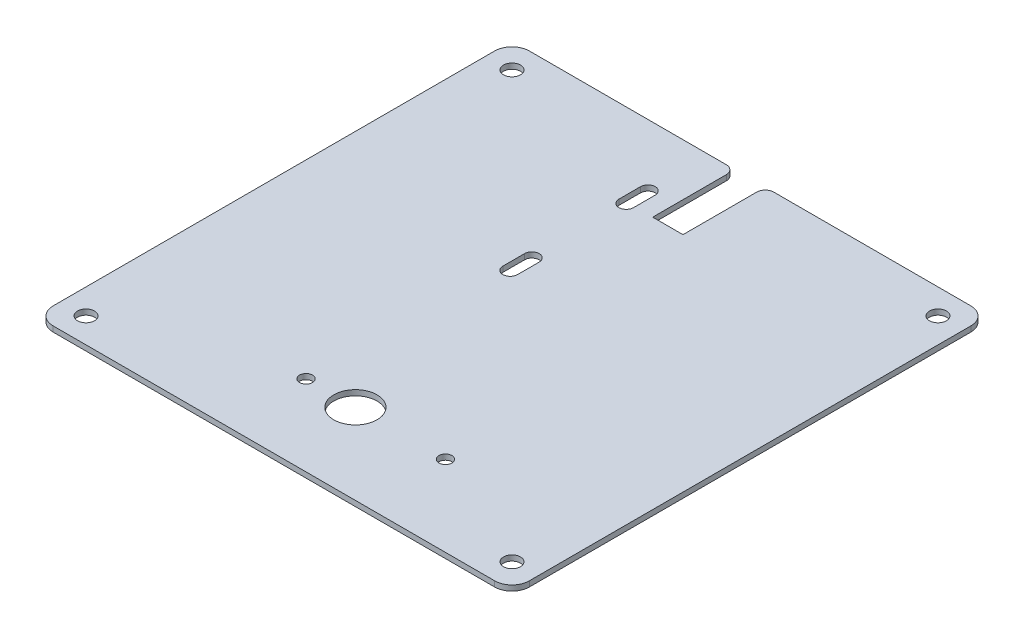
SolidWorks part; units mm, degrees
ref_plane "Front Plane" through (0, 0, 0) normal (0, 0, 1) x (1, 0, 0)
ref_plane "Top Plane" through (0, 0, 0) normal (0, 1, 0) x (1, 0, 0)
ref_plane "Right Plane" through (0, 0, 0) normal (1, 0, 0) x (0, 0, -1)
sketch "Sketch1" plane through (0, 0, 0) normal (0, 1, 0) x (1, 0, 0)
  line L0 (61.03, -65.3659) -> (61.03, 64.1741)
  line L1 (-73.59, -70.4459) -> (55.95, -70.4459)
  line L2 (-78.67, -65.3659) -> (-78.67, 64.1741)
  line L3 (-13.265, 66.7141) -> (-13.265, 45.1241)
  line L4 (-13.265, 45.1241) -> (-4.375, 45.1241)
  line L5 (-4.375, 66.7141) -> (-4.375, 45.1241)
  line L6 (-18.495, 44.7481) -> (-18.495, 51.0981)
  line L7 (-22.8003, 44.7481) -> (-22.8003, 51.0981)
  line L8 (-22.8003, 10.7121) -> (-22.8003, 17.0621)
  line L9 (-18.495, 10.7121) -> (-18.495, 17.0621)
  line L10 (-1.835, 69.2541) -> (55.95, 69.2541)
  line L11 (-73.59, 69.2541) -> (-15.805, 69.2541)
  circle A0 centre (53.664, -63.0799) radius 2.4892
  circle A1 centre (-71.304, 61.8881) radius 2.4892
  circle A2 centre (53.664, 61.8881) radius 2.4892
  circle A3 centre (-71.304, -63.0799) radius 2.4892
  circle A4 centre (-8.566, -46.7941) radius 6.35
  circle A5 centre (17.85, -46.7941) radius 1.905
  circle A6 centre (-23.044, -46.7941) radius 1.905
  arc A7 (55.95, -70.4459) -> (61.03, -65.3659) centre (55.95, -65.3659) ccw
  arc A8 (-78.67, -65.3659) -> (-73.59, -70.4459) centre (-73.59, -65.3659) ccw
  arc A9 (-18.495, 51.0981) -> (-22.8003, 51.0981) centre (-20.6477, 51.0981) ccw
  arc A10 (-22.8003, 44.7481) -> (-18.495, 44.7481) centre (-20.6477, 44.7481) ccw
  arc A11 (-18.495, 17.0621) -> (-22.8003, 17.0621) centre (-20.6477, 17.0621) ccw
  arc A12 (-22.8003, 10.7121) -> (-18.495, 10.7121) centre (-20.6477, 10.7121) ccw
  arc A13 (61.03, 64.1741) -> (55.95, 69.2541) centre (55.95, 64.1741) ccw
  arc A14 (-73.59, 69.2541) -> (-78.67, 64.1741) centre (-73.59, 64.1741) ccw
  arc A15 (-13.265, 66.7141) -> (-15.805, 69.2541) centre (-15.805, 66.7141) ccw
  arc A16 (-1.835, 69.2541) -> (-4.375, 66.7141) centre (-1.835, 66.7141) ccw
extrude "Boss-Extrude1" add sketch "Sketch1" along normal blind 1.5875
